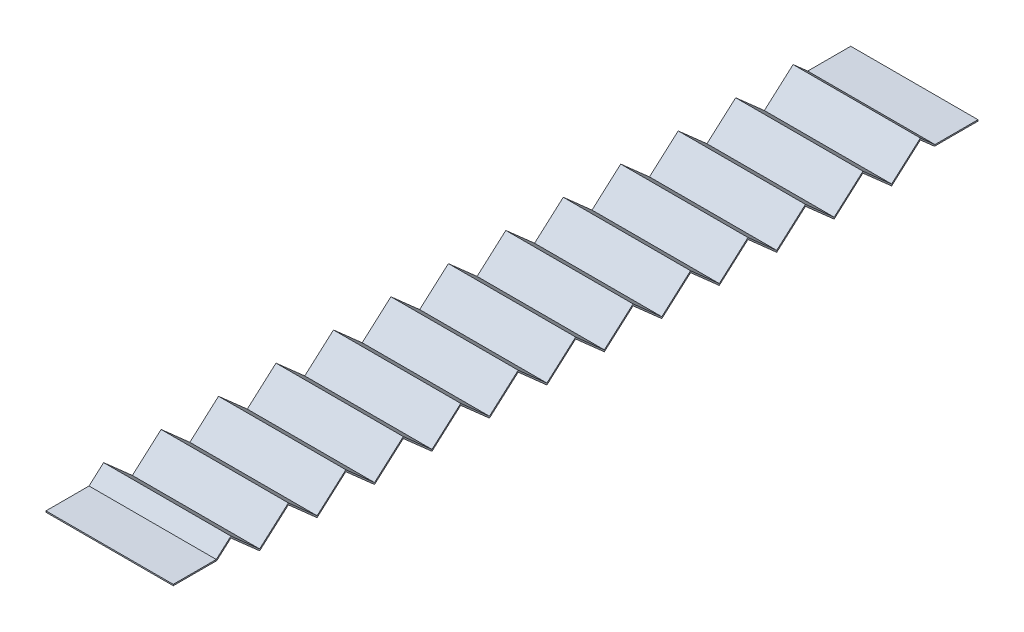
SolidWorks part; units mm, degrees
ref_plane "Front Plane" through (0, 0, 0) normal (0, 0, 1) x (1, 0, 0)
ref_plane "Top Plane" through (0, 0, 0) normal (0, 1, 0) x (1, 0, 0)
ref_plane "Right Plane" through (0, 0, 0) normal (1, 0, 0) x (0, 0, -1)
sketch "Sketch2" plane through (0, 0, 0) normal (0, 0, 1) x (1, 0, 0)
  line L1 (-27.5, 10) -> (27.5, 10)
  line L2 (-27.5, 10) -> (-27.5, 0)
  line L3 (-27.5, 0) -> (27.5, 0)
  line L4 (27.5, 10) -> (27.5, 0)
  point P4 (0, 0)
  dimension "D1" = 10
  dimension "D2" = 55
sketch "Sketch3" plane through (0, 0, 0) normal (1, 0, 0) x (0, 0, -1)
  line L0 (0, 10) -> (316.1578, 10) construction
  line L1 (0, 0) -> (316.1578, 0) construction
  line L3 (17, 5) -> (22.6432, 10)
  line L4 (22.6432, 10) -> (33.9295, 0)
  line L5 (33.9295, 0) -> (45.2158, 10)
  line L6 (45.2158, 10) -> (56.5021, 0)
  line L7 (56.5021, 0) -> (67.7884, 10)
  line L8 (67.7884, 10) -> (79.0747, 0)
  line L9 (79.0747, 0) -> (90.361, 10)
  line L10 (90.361, 10) -> (101.6473, 0)
  line L11 (101.6473, 0) -> (112.9336, 10)
  line L12 (112.9336, 10) -> (124.2199, 0)
  line L13 (124.2199, 0) -> (135.5063, 10)
  line L14 (135.5063, 10) -> (146.7926, 0)
  line L15 (146.7926, 0) -> (158.0789, 10)
  line L16 (158.0789, 10) -> (169.3652, 0)
  line L17 (169.3652, 0) -> (180.6515, 10)
  line L18 (180.6515, 10) -> (191.9378, 0)
  line L19 (0, 10) -> (0, 0) construction
  line L20 (191.9378, 0) -> (203.2241, 10)
  line L21 (203.2241, 10) -> (214.5104, 0)
  line L22 (214.5104, 0) -> (225.7967, 10)
  line L23 (225.7967, 10) -> (237.083, 0)
  line L24 (237.083, 0) -> (248.3694, 10)
  line L25 (248.3694, 10) -> (259.6557, 0)
  line L26 (259.6557, 0) -> (270.942, 10)
  line L27 (270.942, 10) -> (282.2283, 0)
  line L28 (282.2283, 0) -> (293.5146, 10)
  line L29 (293.5146, 10) -> (299.1578, 5)
  line L30 (316.1578, 10) -> (316.1578, 0) construction
  line L31 (17, 5) -> (0, 5)
  line L32 (299.1578, 5) -> (316.1578, 5)
  line L34 (316.1578, 4.75) -> (316.1578, 22.75) construction
  dimension "D2" = 17
  dimension "D1" = 10
  dimension "D3" = 17
extrude "Extrude-Thin1" add sketch "Sketch3" against normal mid plane 50 thin thin type mid plane wall 0.5
